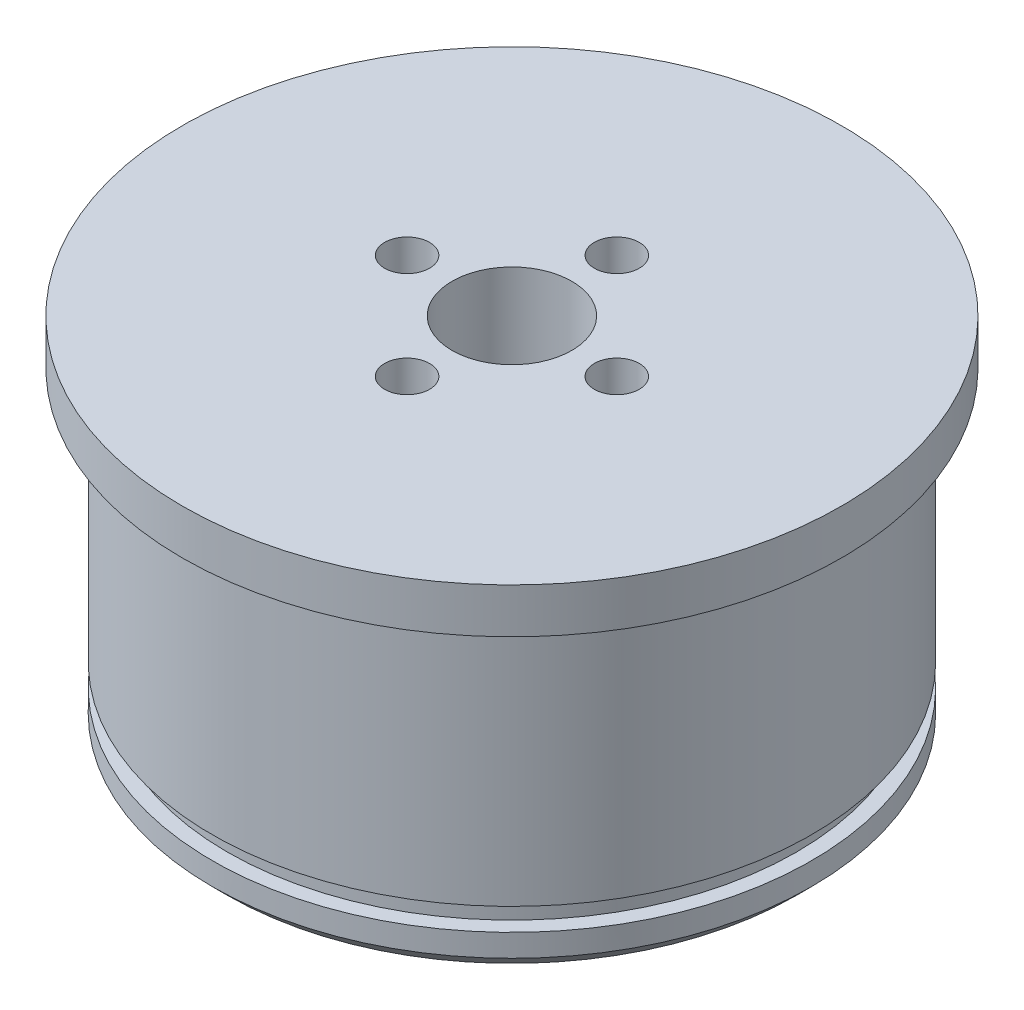
SolidWorks part; units mm, degrees
material "1060 Сплав"
ref_plane "Спереди" through (0, 0, 0) normal (0, 0, 1) x (1, 0, 0)
ref_plane "Сверху" through (0, 0, 0) normal (0, 1, 0) x (1, 0, 0)
ref_plane "Справа" through (0, 0, 0) normal (1, 0, 0) x (0, 0, -1)
sketch "Эскиз1" plane through (0, 0, 0) normal (0, 1, 0) x (1, 0, 0)
  circle A0 centre (0, 0) radius 20
  dimension "D1" = 40
extrude "Бобышка-Вытянуть1" add sketch "Эскиз1" along normal blind 21
sketch "Эскиз2" plane through (0, 0, 0) normal (0, -1, 0) x (1, 0, 0)
  circle A0 centre (0, 0) radius 10
  dimension "D1" = 20
extrude "Вырез-Вытянуть2" cut sketch "Эскиз2" against normal blind 2.5
ref_plane "Плоскость1" through (0, 2.5, 0) normal (0, -1, 0) x (-1, 0, 0)
sketch "Эскиз5" plane through (0, 2.5, 0) normal (0, -1, 0) x (-1, 0, 0)
  circle A0 centre (0, 0) radius 19
  circle A1 centre (0, 0) radius 20
  dimension "D1" = 38
  dimension "D2" = 40
extrude "Вырез-Вытянуть5" cut sketch "Эскиз5" against normal blind 1.5
chamfer "Фаска1" distance 1 angle 45 1 edges at (0, 0, 20)
sketch "Эскиз6" plane through (0, 21, 0) normal (0, 1, 0) x (1, 0, 0)
  circle A0 centre (0, 0) radius 22
  dimension "D1" = 44
extrude "Бобышка-Вытянуть2" add sketch "Эскиз6" along normal blind 3
sketch "Эскиз4" plane through (0, 2.5, 0) normal (0, -1, 0) x (1, 0, 0)
  circle A0 centre (0, 7) radius 1.5
  dimension "D2" = 3
  dimension "D1" = 7
extrude "Вырез-Вытянуть6" cut sketch "Эскиз4" against normal through all
pattern_circular "Круговой массив1" count 4 over 360 about axis through (0, 2.5, 0) along (0, -1, 0) of "Вырез-Вытянуть6" reverse direction yes
sketch "Эскиз7" plane through (0, 24, 0) normal (0, 1, 0) x (1, 0, 0)
  circle A0 centre (0, 0) radius 4
extrude "Вырез-Вытянуть7" cut sketch "Эскиз7" against normal through all
